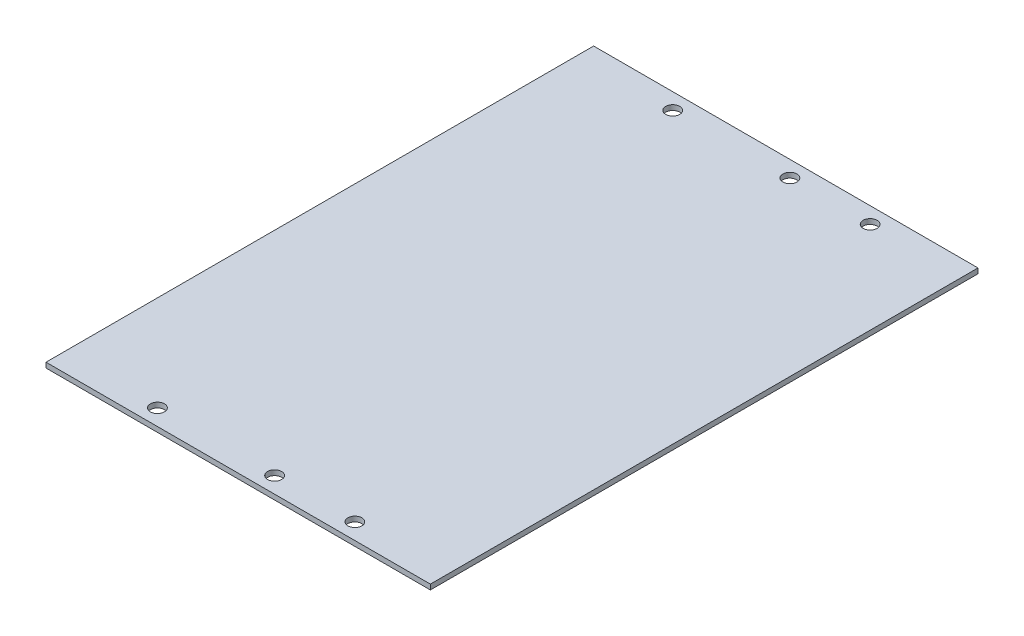
SolidWorks part; units mm, degrees
material "Zoltek Panex 33"
ref_plane "Front Plane" through (0, 0, 0) normal (0, 0, 1) x (1, 0, 0)
ref_plane "Top Plane" through (0, 0, 0) normal (0, 1, 0) x (1, 0, 0)
ref_plane "Right Plane" through (0, 0, 0) normal (1, 0, 0) x (0, 0, -1)
sketch "Sketch1" plane through (0, 0, 0) normal (0, 1, 0) x (1, 0, 0)
  line L0 (138.9, 215) -> (138.9, 202.3) construction
  line L1 (0, 0) -> (150.9, 0)
  line L2 (0, 0) -> (0, 215)
  line L3 (0, 215) -> (150.9, 215)
  line L4 (150.9, 0) -> (150.9, 215)
  line L5 (13.4, 202.3) -> (13.4, 215) construction
  line L7 (83.4, 163.1015) -> (83.4, 51.9035) construction
  line L8 (43.9375, 107.5025) -> (122.8625, 107.5025) construction
  circle A0 centre (37.4, 208.65) radius 2.75
  circle A1 centre (83.4, 208.65) radius 2.75
  circle A2 centre (114.9, 208.65) radius 2.75
  circle A3 centre (114.9, 6.355) radius 2.75
  circle A4 centre (83.4, 6.355) radius 2.75
  circle A5 centre (37.4, 6.355) radius 2.75
  point P11 (0, 0)
  dimension "D3" = 6.35
  dimension "D4" = 5.5
  dimension "D5" = 24
  dimension "D6" = 24
  dimension "D7" = 0
  dimension "D1" = 150.9
  dimension "D2" = 215
extrude "Boss-Extrude1" add sketch "Sketch1" along normal blind 2
